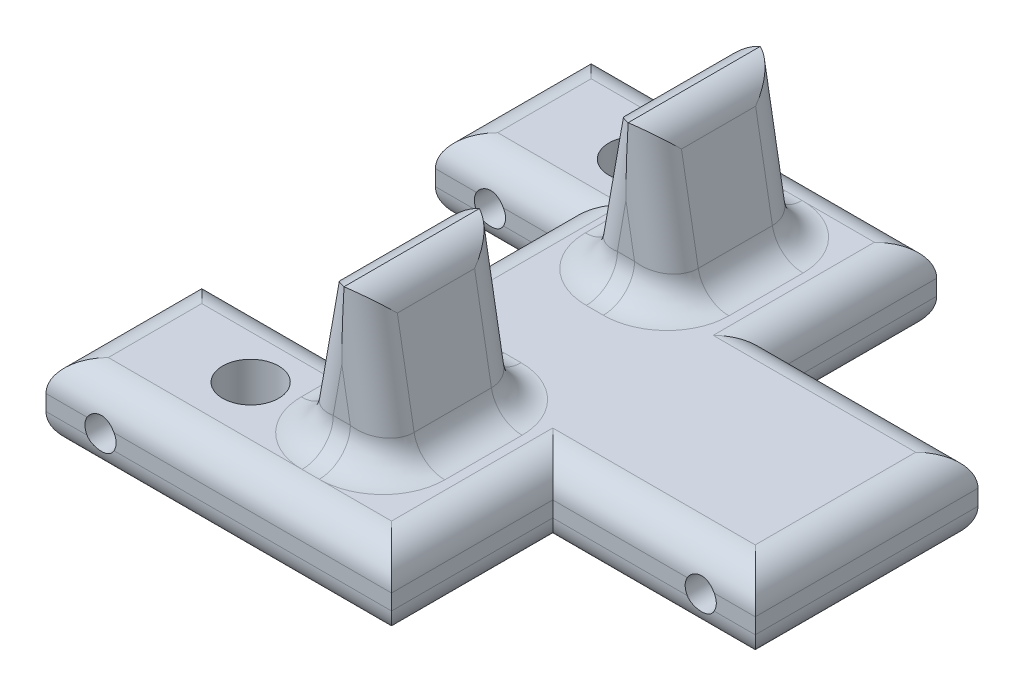
SolidWorks part; units mm, degrees
ref_plane "Front Plane" through (0, 0, 0) normal (0, 0, 1) x (1, 0, 0)
ref_plane "Top Plane" through (0, 0, 0) normal (0, 1, 0) x (1, 0, 0)
ref_plane "Right Plane" through (0, 0, 0) normal (1, 0, 0) x (0, 0, -1)
sketch "Sketch1" plane through (0, 0, 0) normal (0, 1, 0) x (1, 0, 0)
  line L0 (-14.9914, 7.3995) -> (-9.4914, 7.3995)
  line L1 (-14.9914, -17.6005) -> (7.1908, -17.6005)
  line L2 (-14.9914, -17.6005) -> (-14.9914, -7.6005)
  line L3 (-14.9914, 17.3995) -> (7.1908, 17.3995)
  line L7 (-6.9914, 7.3995) -> (-6.9914, 2.5018)
  line L8 (-6.9914, -7.6005) -> (-9.4914, -7.6005)
  line L9 (-14.9914, 7.3995) -> (-14.9914, 17.3995)
  line L10 (7.1908, 17.3995) -> (7.1908, 7.0495)
  line L12 (7.1908, -17.6005) -> (7.1908, -7.2505)
  line L28 (-6.9914, -2.5018) -> (-6.9914, -7.6005)
  line L31 (-9.4914, 7.3995) -> (-6.9914, 7.3995)
  line L32 (-9.4914, -7.6005) -> (-14.9914, -7.6005)
  line L33 (-6.9914, 2.5018) -> (-6.9914, -2.5018)
  line L34 (7.1908, 7.0495) -> (20.1908, 7.0495)
  line L35 (20.1908, 7.0495) -> (20.1908, -7.2505)
  line L36 (20.1908, -7.2505) -> (7.1908, -7.2505)
  point P0 (0, 0)
  dimension "D1" = 13
  dimension "D2" = 35
  dimension "D3" = 10
  dimension "D4" = 10.35
  dimension "D5" = 8
  dimension "D6" = 22.1822
  dimension "D9" = 2.5
extrude "Boss-Extrude1" add sketch "Sketch1" along normal blind 5
sketch "Sketch5" plane through (0, 0, 17.6005) normal (0, 0, 1) x (1, 0, 0)
  line L0 (-17.6008, 2.5) -> (1.9314, 2.5) construction
  line L1 (-6.9914, 0) -> (-14.9914, 0) construction
  line L2 (-6.9914, 5) -> (-14.9914, 5) construction
  line L4 (-14.9914, 5) -> (-14.9914, 0) construction
  circle A0 centre (-11.4914, 2.5) radius 1
  dimension "D1" = 3.5
  dimension "2" = 2
extrude "Cut-Extrude1" cut sketch "Sketch5" against normal blind 42
sketch "Sketch6" plane through (0, 0, 7.2505) normal (0, 0, 1) x (1, 0, 0)
  line L0 (26.3292, 2.5) -> (6.5316, 2.5) construction
  line L1 (7.1908, 5) -> (20.1908, 5) construction
  line L2 (7.1908, 0) -> (20.1908, 0) construction
  line L3 (20.1908, 5) -> (20.1908, 0) construction
  circle A0 centre (16.6908, 2.5) radius 1
  dimension "D1" = 2
  dimension "D2" = 3.5
sketch "Sketch9" plane through (0, 0, 17.6005) normal (0, 0, 1) x (1, 0, 0)
  line L0 (0, 8.3909) -> (0, -6.7923) construction
  line L1 (-2.9321, 5) -> (-1.274, 14.4032)
  line L2 (-14.9914, 5) -> (7.1908, 5) construction
  line L3 (-1.274, 14.4032) -> (1.274, 14.4032)
  line L4 (1.274, 14.4032) -> (2.9321, 5)
  line L5 (2.9321, 5) -> (-2.9321, 5)
  dimension "D1" = 100
extrude "Boss-Extrude3" add sketch "Sketch9" against normal blind 27 from offset 4 offset against normal yes
sketch "Sketch10" plane through (20.1908, 0, 0) normal (1, 0, 0) x (0, 0, -1)
  line L0 (-7.2505, 5) -> (7.0495, 5) construction
  line L1 (-4.6394, 17.2402) -> (4.6394, 17.2402)
  line L2 (-4.6394, 17.2402) -> (-4.6394, 5)
  line L3 (-4.6394, 5) -> (4.6394, 5)
  line L4 (4.6394, 17.2402) -> (4.6394, 5)
  line L5 (0, 15.8304) -> (0, -3.5317) construction
extrude "Cut-Extrude4" cut sketch "Sketch10" against normal blind 27
fillet "Fillet3" radius 2 44 edges at (-1.274, 14.4032, 9.1199) (-2.1031, 9.7016, 13.6005) (-2.1031, 9.7016, 4.6394) (-2.1031, 9.7016, -13.3995) (-1.274, 14.4032, -9.0194) (-2.1031, 9.7016, -4.6394) (1.274, 14.4032, -9.0194) (2.1031, 9.7016, -13.3995) (2.1031, 9.7016, -4.6394) (2.1031, 9.7016, 13.6005) (1.274, 14.4032, 9.1199) (2.1031, 9.7016, 4.6394) (20.1908, 0, 0.1005) (13.6908, 0, -7.0495) (7.1908, 0, -12.2245) (-3.9003, 0, -17.3995) (-14.9914, 0, -12.3995) (-10.9914, 0, -7.3995) (-6.9914, 0, 0.1005) (-10.9914, 0, 7.6005) (-14.9914, 0, 12.6005) (-3.9003, 0, 17.6005) (7.1908, 0, 12.4255) (13.6908, 0, 7.2505) (13.6908, 5, 7.2505) (7.1908, 5, 12.4255) (-3.9003, 5, 17.6005) (-14.9914, 5, 12.6005) (-10.9914, 5, 7.6005) (-6.9914, 5, 0.1005) (-10.9914, 5, -7.3995) (-14.9914, 5, -12.3995) (-3.9003, 5, -17.3995) (7.1908, 5, -12.2245) (13.6908, 5, -7.0495) (20.1908, 5, 0.1005) (2.9321, 5, -9.0194) (0, 5, -13.3995) (-2.9321, 5, -9.0194) (0, 5, -4.6394) (-2.9321, 5, 9.1199) (0, 5, 13.6005) (2.9321, 5, 9.1199) (0, 5, 4.6394)
extrude "Cut-Extrude6" cut sketch "Sketch6" against normal blind 15
sketch "Sketch12" plane through (0, 5, 0) normal (0, 1, 0) x (1, 0, 0)
  line L0 (-20.673, 0) -> (32.4431, 0) construction
  line L1 (-17.7731, 12.3995) -> (1.682, 12.3995) construction
  line L2 (-0.5486, 15.3995) -> (-12.9914, 15.3995) construction
  line L3 (-12.9914, 9.3995) -> (-4.9914, 9.3995) construction
  circle A0 centre (-7.0545, 12.3995) radius 1.8
  circle A1 centre (-7.0545, -12.3995) radius 1.8
  dimension "D1" = 3.6
extrude "Cut-Extrude7" cut sketch "Sketch12" against normal blind 10
